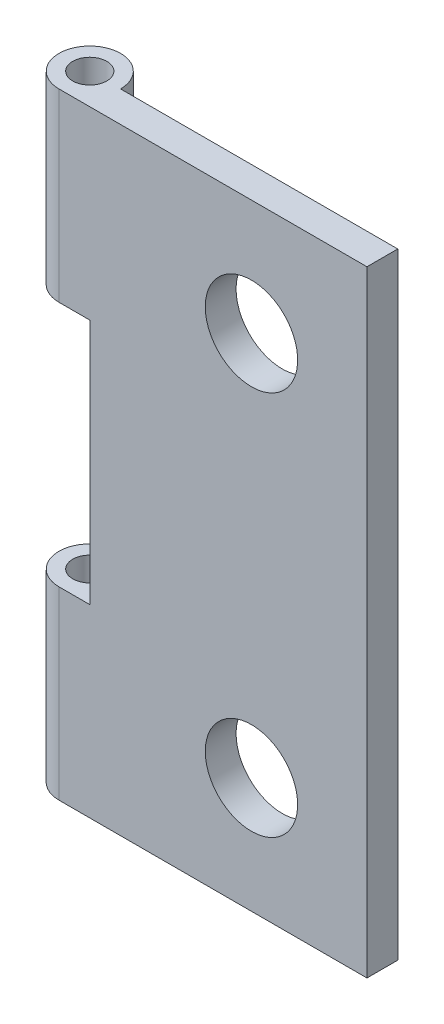
SolidWorks part; units mm, degrees
ref_plane "前视基准面" through (0, 0, 0) normal (0, 0, 1) x (1, 0, 0)
ref_plane "上视基准面" through (0, 0, 0) normal (0, 1, 0) x (1, 0, 0)
ref_plane "右视基准面" through (0, 0, 0) normal (1, 0, 0) x (0, 0, -1)
other "Configuration Table"
sketch "草图1" plane through (0, 0, 0) normal (0, 1, 0) x (1, 0, 0)
  line L1 (-10, 1) -> (10, 1)
  line L2 (-10, 1) -> (-10, -1)
  line L3 (-10, -1) -> (10, -1)
  line L4 (10, 1) -> (10, -1)
  line L5 (-10, 1) -> (10, -1) construction
  line L6 (-10, -1) -> (10, 1) construction
  circle A0 centre (-10, 1) radius 2
  circle A1 centre (-10, 1) radius 1.1074
  point P0 (0, 0)
extrude "凸台-拉伸1" add sketch "草图1" along normal blind 40 contours L1 A0 L2 | A0 L3 L4 L1 | L2 A0 L1 region at (-10.8231, 0, -1.8231) region at (-8.9837, 0, 0.0163) region at (0.78, 0, 0.0129)
sketch "草图3" plane through (0, 0, -1) normal (0, 0, -1) x (-1, 0, 0)
  line L0 (8, 40) -> (8, 0) construction
  line L1 (8, 20) -> (12, 20)
  line L2 (8, 20) -> (8, 28)
  line L3 (8, 28) -> (12, 28)
  line L4 (12, 20) -> (12, 28)
  line L5 (12, 0) -> (12, 40) construction
  line L7 (8, 20) -> (12, 20)
  line L8 (8, 20) -> (8, 12)
  line L9 (8, 12) -> (12, 12)
  line L10 (12, 20) -> (12, 12)
  line M3 (8, 0) -> (8, 40)
extrude "切除-拉伸1" cut sketch "草图3" against normal blind 40 and the other way blind 40 contours L1 L4 L3 M3 | L10 L1 L9 M3 region at (-10, 24, -1) region at (-10, 16, -1)
sketch "草图5" plane through (0, 0, -1) normal (0, 0, -1) x (-1, 0, 0)
  line L1 (-10, 0) -> (-2.5, 0)
  line L2 (-10, 0) -> (-10, 7.5)
  line L3 (-10, 7.5) -> (-2.5, 7.5)
  line L4 (-2.5, 0) -> (-2.5, 7.5)
  line L5 (-10, 40) -> (-2.5, 40)
  line L6 (-10, 40) -> (-10, 32.5)
  line L7 (-10, 32.5) -> (-2.5, 32.5)
  line L8 (-2.5, 40) -> (-2.5, 32.5)
  circle A0 centre (-2.5, 32.5) radius 3
  circle A1 centre (-2.5, 7.5) radius 3
extrude "切除-拉伸2" cut sketch "草图5" against normal blind 10 contours L8 A0 L7 | L7 A0 L8 | L4 A1 L3 | L3 A1 L4 region at (3.7732, 6.2268, -1) region at (2.0756, 7.9244, -1) region at (2.0756, 32.0756, -1) region at (3.7732, 33.7732, -1)
